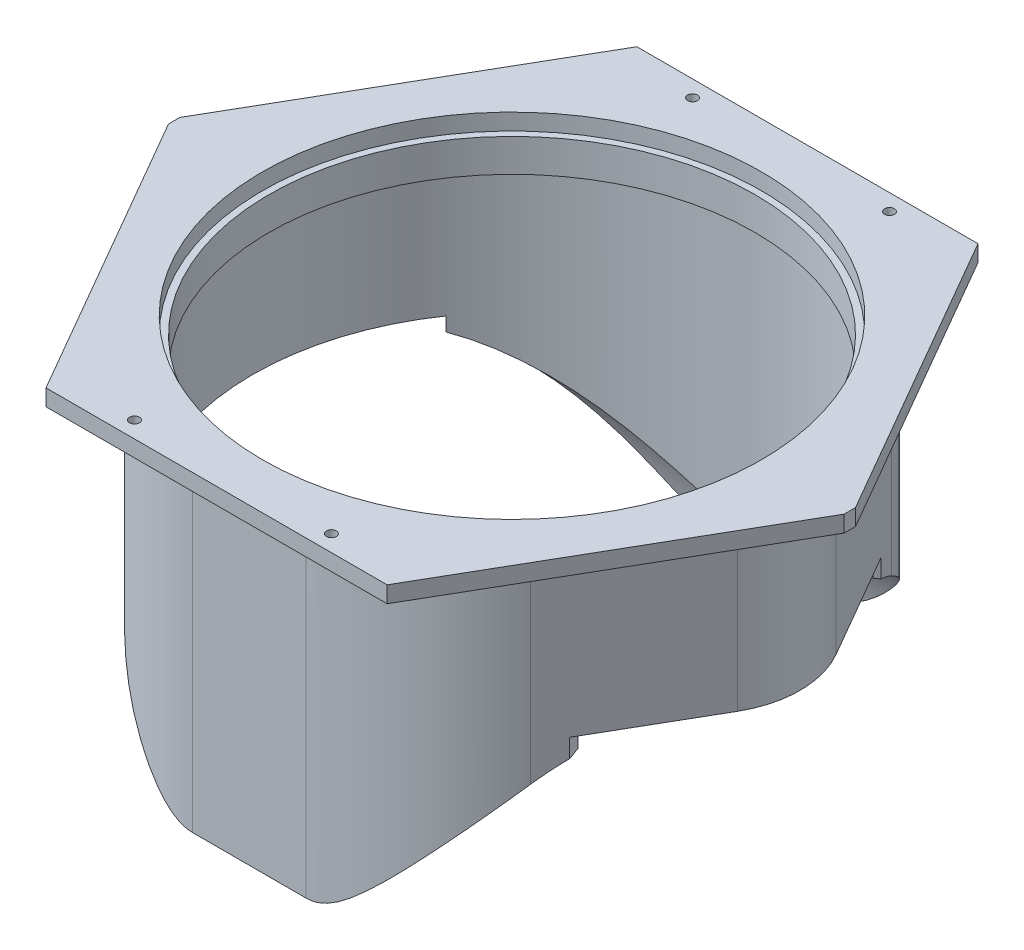
SolidWorks part; units mm, degrees
ref_plane "Front Plane" through (0, 0, 0) normal (0, 0, 1) x (1, 0, 0)
ref_plane "Top Plane" through (0, 0, 0) normal (0, 1, 0) x (1, 0, 0)
ref_plane "Right Plane" through (0, 0, 0) normal (1, 0, 0) x (0, 0, -1)
sketch "Sketch1" plane through (0, 0, 0) normal (0, 1, 0) x (1, 0, 0)
  line L1 (103.923, 0) -> (51.9615, 90)
  line L2 (51.9615, 90) -> (-51.9615, 90)
  line L3 (-51.9615, 90) -> (-103.923, 0)
  line L4 (-103.923, 0) -> (-51.9615, -90)
  line L5 (-51.9615, -90) -> (51.9615, -90)
  line L6 (51.9615, -90) -> (103.923, 0)
  circle A0 centre (0, 0) radius 76
  arc A1 (28.5424, 85.3542) -> (-28.5424, 85.3542) centre (0, 0) ccw construction
  circle A2 centre (30, 85) radius 1.5
  circle A3 centre (-30, 85) radius 1.5
  circle A4 centre (30, -85) radius 1.5
  circle A5 centre (-30, -85) radius 1.5
  arc A6 (-31.357, 84.3608) -> (-31.357, -84.3608) centre (0, 0) ccw construction
  arc A7 (-28.5424, -85.3542) -> (28.5424, -85.3542) centre (0, 0) ccw construction
  arc A8 (31.357, -84.3608) -> (31.357, 84.3608) centre (0, 0) ccw construction
  dimension "D1" = 152
  dimension "D9" = 3
  dimension "D10" = 3
  dimension "D11" = 3
  dimension "D12" = 3
  dimension "D2" = 180
extrude "Boss-Extrude1" add sketch "Sketch1" along normal blind 5
sketch "Sketch2" plane through (0, 0, 0) normal (0, -1, 0) x (1, 0, 0)
  line L1 (92.376, 0) -> (46.188, 80)
  line L2 (46.188, 80) -> (-46.188, 80)
  line L3 (-46.188, 80) -> (-92.376, 0)
  line L4 (-92.376, 0) -> (-46.188, -80)
  line L5 (-46.188, -80) -> (46.188, -80)
  line L6 (46.188, -80) -> (92.376, 0)
  circle A8 centre (0, 0) radius 74
  dimension "D1" = 148
  dimension "D3" = 160
extrude "Boss-Extrude2" add sketch "Sketch2" along normal blind 50
sketch "Sketch3" plane through (0, -50, 0) normal (0, -1, 0) x (1, 0, 0)
  line L0 (0, 74) -> (0, 80)
  line L1 (0, -74) -> (0, -80)
  line L4 (65, 35.3695) -> (65, 47.4167)
  line L5 (65, -35.3695) -> (65, -47.4167)
  line L6 (-65, 35.3695) -> (-65, 47.4167)
  line L7 (-65, -35.3695) -> (-65, -47.4167)
  line L8 (-46.188, 80) -> (-65, 47.4167)
  line L10 (-46.188, 80) -> (46.188, 80)
  line L11 (46.188, 80) -> (65, 47.4167)
  line L13 (0, -80) -> (46.188, -80)
  line L14 (46.188, -80) -> (65, -47.4167)
  line L16 (0, -80) -> (-46.188, -80)
  line L17 (-46.188, -80) -> (-65, -47.4167)
  arc A0 (65, 35.3695) -> (-65, 35.3695) centre (0, 0) ccw
  arc A1 (-65, -35.3695) -> (65, -35.3695) centre (0, 0) ccw
  line M7 (46.188, -80) -> (92.376, 0)
  line M8 (92.376, 0) -> (46.188, 80)
  line M9 (46.188, 80) -> (-46.188, 80)
  line M10 (-46.188, 80) -> (-92.376, 0)
  line M11 (-92.376, 0) -> (-46.188, -80)
  line M12 (-46.188, -80) -> (46.188, -80)
  circle M13 centre (0, 0) radius 74
  dimension "D1" = 80
  dimension "D2" = 80
extrude "Boss-Extrude3" add sketch "Sketch3" along normal blind 50 contours L5 L1 M13 M12 M7 | L4 L0 M13 M8 M9 | L6 L0 M13 M9 M10 | L7 L1 M13 M11 M12 region at (-37.9821, -50, 67.6199) region at (37.9821, -50, 67.6199) region at (-37.9821, -50, -67.6199) region at (37.9821, -50, -67.6199)
fillet "Fillet1" radius 30 1 edges at (92.376, -25, 0)
fillet "Fillet2" radius 30 1 edges at (-92.376, -25, 0)
sketch "Sketch4" plane through (0, 5, 0) normal (0, 1, 0) x (1, 0, 0)
  line L0 (-103.923, 0) -> (-102.923, 0)
  line L1 (-102.923, 0) -> (-102.923, 15.9835)
  line L2 (-102.923, 15.9835) -> (-112.2362, 15.9835)
  line L3 (-112.2362, 15.9835) -> (-112.2362, -18.5005)
  line L4 (-112.2362, -18.5005) -> (-102.923, -18.5005)
  line L5 (-102.923, -18.5005) -> (-102.923, 0)
  line L6 (103.923, 0) -> (102.923, 0)
  line L7 (102.923, 0) -> (102.923, 26.8069)
  line L8 (102.923, 26.8069) -> (114.2499, 26.8069)
  line L9 (114.2499, 26.8069) -> (114.2499, -39.3923)
  line L10 (114.2499, -39.3923) -> (102.923, -39.3923)
  line L11 (102.923, -39.3923) -> (102.923, 0)
  line M5 (51.9615, -90) -> (103.923, 0)
  line M6 (103.923, 0) -> (51.9615, 90)
  line M8 (-51.9615, 90) -> (-103.923, 0)
  line M9 (-103.923, 0) -> (-51.9615, -90)
  dimension "D1" = 1
  dimension "D2" = 1
extrude "Cut-Extrude2" cut sketch "Sketch4" against normal blind 10 contours L0 L1 M8 | L5 L0 M9 | L11 L6 M5 | L7 L6 M6 region at (-103.2564, 5, -0.5774) region at (-103.2564, 5, 0.5774) region at (103.2564, 5, 0.5774) region at (103.2564, 5, -0.5774)
sketch "Sketch5" plane through (102.923, 0, 0) normal (1, 0, 0) x (0, 0, -1)
  line L0 (-35.3695, -50) -> (35.3695, -50)
  line L1 (80, -100) -> (-80, -100)
  arc A0 (-80, -100) -> (-35.3695, -50) centre (-11.8356, -115.9254) cw
  arc A1 (80, -100) -> (35.3695, -50) centre (11.8356, -115.9254) ccw
  dimension "D1" = 70
  dimension "D2" = 70
extrude "Cut-Extrude3" cut sketch "Sketch5" against normal blind 211
fillet "Fillet3" radius 50 4 edges at (46.188, -50, 80) (-46.188, -50, 80) (46.188, -50, -80) (-46.188, -50, -80)
sketch "Sketch7" plane through (0, -50, 0) normal (0, -1, 0) x (1, 0, 0)
  circle A0 centre (0, 0) radius 79
  dimension "D1" = 158
extrude "Cut-Extrude4" cut sketch "Sketch7" against normal blind 40 and the other way blind 50
